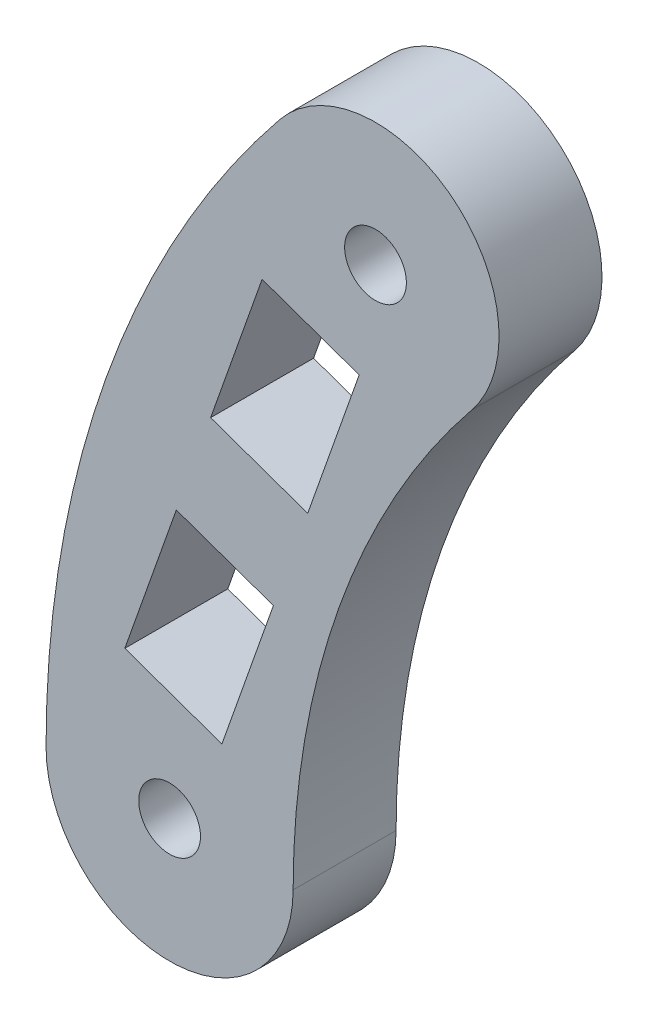
SolidWorks part; units mm, degrees
ref_plane "Plan de face" through (0, 0, 0) normal (0, 0, 1) x (1, 0, 0)
ref_plane "Plan de dessus" through (0, 0, 0) normal (0, 1, 0) x (1, 0, 0)
ref_plane "Plan de droite" through (0, 0, 0) normal (1, 0, 0) x (0, 0, -1)
sketch "Esquisse1" plane through (0, 0, 0) normal (0, 0, 1) x (1, 0, 0)
  line L0 (-35, 28.2843) -> (0, 0) construction
  line L1 (0, 0) -> (-45, 0) construction
  line L2 (-47.0298, -1.0204) -> (-35.9733, 30.2522) construction
  line L3 (0, 0) -> (-42.4264, 15) construction
  line L4 (-35.7932, 23.2614) -> (-38.2932, 16.1904)
  line L5 (-38.2932, 16.1904) -> (-43.0073, 17.857)
  line L6 (-43.0073, 17.857) -> (-40.5073, 24.9281)
  line L7 (-40.5073, 24.9281) -> (-35.7932, 23.2614)
  line L8 (-47.174, 6.0719) -> (-42.4599, 4.4052)
  line L9 (-44.674, 13.143) -> (-47.174, 6.0719)
  line L10 (-39.9599, 11.4763) -> (-44.674, 13.143)
  line L11 (-42.4599, 4.4052) -> (-39.9599, 11.4763)
  arc A0 (-45, 0) -> (-35, 28.2843) centre (0, 0) cw construction
  arc A1 (-39.6667, 32.0555) -> (-51, 0) centre (0, 0) ccw
  arc A2 (-30.3333, 24.513) -> (-39, 0) centre (0, 0) ccw
  arc A3 (-30.3333, 24.513) -> (-39.6667, 32.0555) centre (-35, 28.2843) ccw
  arc A4 (-51, 0) -> (-39, 0) centre (-45, 0) ccw
  circle A5 centre (-35, 28.2843) radius 1.5
  circle A6 centre (-45, 0) radius 1.5
  point P4 (-42.4264, 15)
  dimension "D1" = 30
  dimension "D2" = 3
  dimension "D3" = 6
  dimension "D4" = 45
  dimension "D5" = 1
  dimension "D6" = 7.5
  dimension "D7" = 5
  dimension "D8" = 2.5
extrude "Boss.-Extru.1" add sketch "Esquisse1" along normal blind 5
